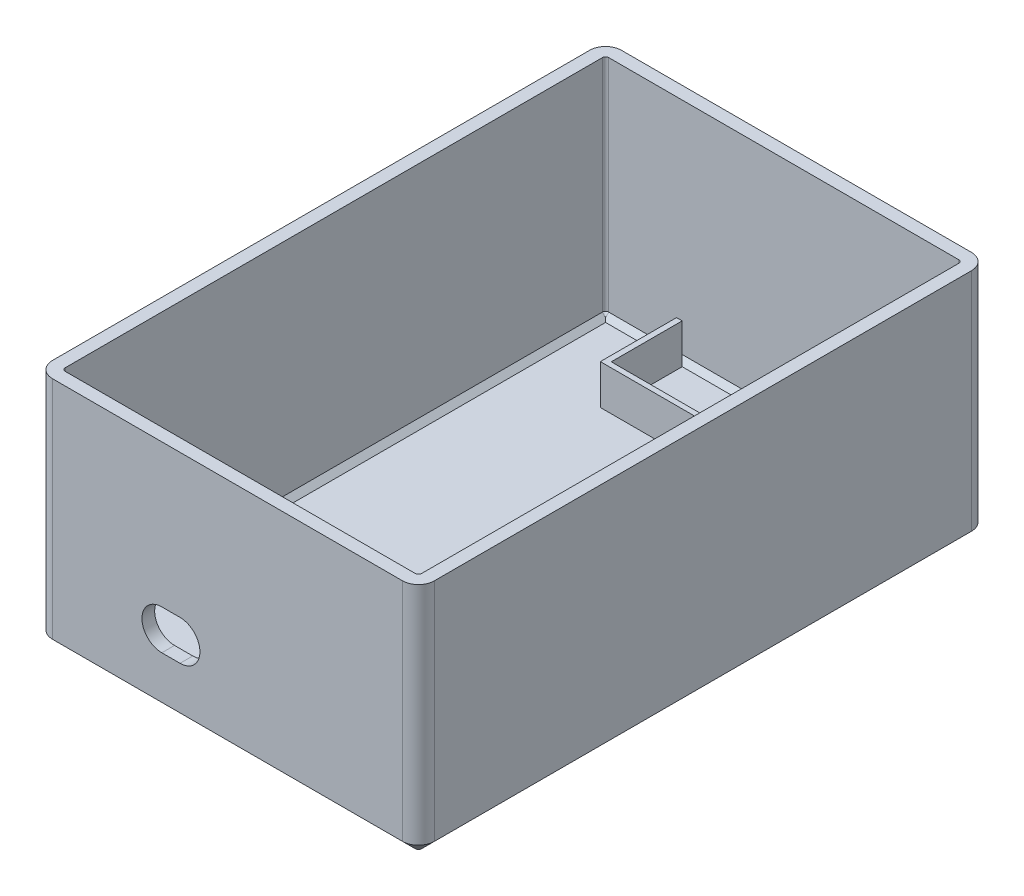
SolidWorks part; units mm, degrees
ref_plane "Front Plane" through (0, 0, 0) normal (0, 0, 1) x (1, 0, 0)
ref_plane "Top Plane" through (0, 0, 0) normal (0, 1, 0) x (1, 0, 0)
ref_plane "Right Plane" through (0, 0, 0) normal (1, 0, 0) x (0, 0, -1)
sketch "Sketch1" plane through (0, 0, 0) normal (0, 1, 0) x (1, 0, 0)
  line L1 (-25.5282, 55.8435) -> (70.5636, 55.8435)
  line L2 (-25.5282, 55.8435) -> (-25.5282, -87.3412)
  line L3 (-25.5282, -87.3412) -> (70.5636, -87.3412)
  line L4 (70.5636, 55.8435) -> (70.5636, -87.3412)
  dimension "D1" = 96.0917
extrude "Boss-Extrude1" add sketch "Sketch1" along normal blind 60
fillet "Fillet1" radius 4 4 edges at (70.5636, 30, -55.8435) (70.5636, 30, 87.3412) (-25.5282, 30, 87.3412) (-25.5282, 30, -55.8435)
chamfer "Chamfer1" distance 3.2 angle 45 8 edges at (22.5177, 0, -55.8435) (-25.5282, 0, 15.7489) (22.5177, 0, 87.3412) (-24.3566, 0, 86.1697) (-24.3566, 0, -54.6719) (69.392, 0, 86.1697) (69.392, 0, -54.6719) (70.5636, 0, 15.7489)
shell "Shell2" thickness 3.2 removed face at (22.5177, 60, 15.7489)
sketch "Sketch2" plane through (0, 0, 87.3412) normal (0, 0, 1) x (1, 0, 0)
  line L0 (5.9734, 19.0214) -> (10.5603, 19.0214) construction
  line L1 (5.9734, 24.0214) -> (10.5603, 24.0214)
  line L2 (5.9734, 14.0214) -> (10.5603, 14.0214)
  arc A0 (5.9734, 24.0214) -> (5.9734, 14.0214) centre (5.9734, 19.0214) ccw
  arc A1 (10.5603, 14.0214) -> (10.5603, 24.0214) centre (10.5603, 19.0214) ccw
  spline S0 degree 5 poles (8.2168, 16.6) (7.51, 16.6) (6.8025, 16.8768) (6.2436, 17.4363) (5.6901, 18.85) (6.2436, 20.2637) (6.8025, 20.8232) (7.51, 21.1) (8.2168, 21.1) knots 0 0 0 0 0 0 0.003511 0.003511 0.003511 0.007022 0.007022 0.007022 0.007022 0.007022 0.007022 weights 1 1 1 1 1 1 1 1 1 construction
  spline S1 degree 5 poles (8.3168, 16.6) (9.0237, 16.6) (9.7312, 16.8768) (10.2901, 17.4363) (10.8436, 18.85) (10.2901, 20.2637) (9.7312, 20.8232) (9.0237, 21.1) (8.3168, 21.1) knots 0 0 0 0 0 0 0.003511 0.003511 0.003511 0.007022 0.007022 0.007022 0.007022 0.007022 0.007022 weights 1 1 1 1 1 1 1 1 1 construction
  point P6 (8.2668, 19.0214)
extrude "Cut-Extrude1" cut sketch "Sketch2" against normal up to next
sketch "Sketch4" plane through (0, 3.2, 0) normal (0, 1, 0) x (1, 0, 0)
  line L0 (-21.0027, 51.318) -> (66.0381, 51.318) construction
  line L1 (66.0209, 51.318) -> (-3.1262, 51.318)
  line L2 (66.0209, 51.318) -> (66.0209, 32.1256)
  line L3 (66.0209, 32.1256) -> (-3.1262, 32.1256)
  line L4 (-3.1262, 51.318) -> (-3.1262, 32.1256)
extrude "Boss-Extrude2" add sketch "Sketch4" along normal blind 10
sketch "Sketch6" plane through (0, 13.2, 0) normal (0, 1, 0) x (1, 0, 0)
  line L0 (66.0209, 51.318) -> (-3.1262, 51.318) construction
  line L1 (-1.7095, 51.318) -> (65.6529, 51.318)
  line L2 (-1.7095, 51.318) -> (-1.7095, 33.4579)
  line L3 (-1.7095, 33.4579) -> (65.6529, 33.4579)
  line L4 (65.6529, 51.318) -> (65.6529, 33.4579)
extrude "Cut-Extrude2" cut sketch "Sketch6" against normal blind 10
